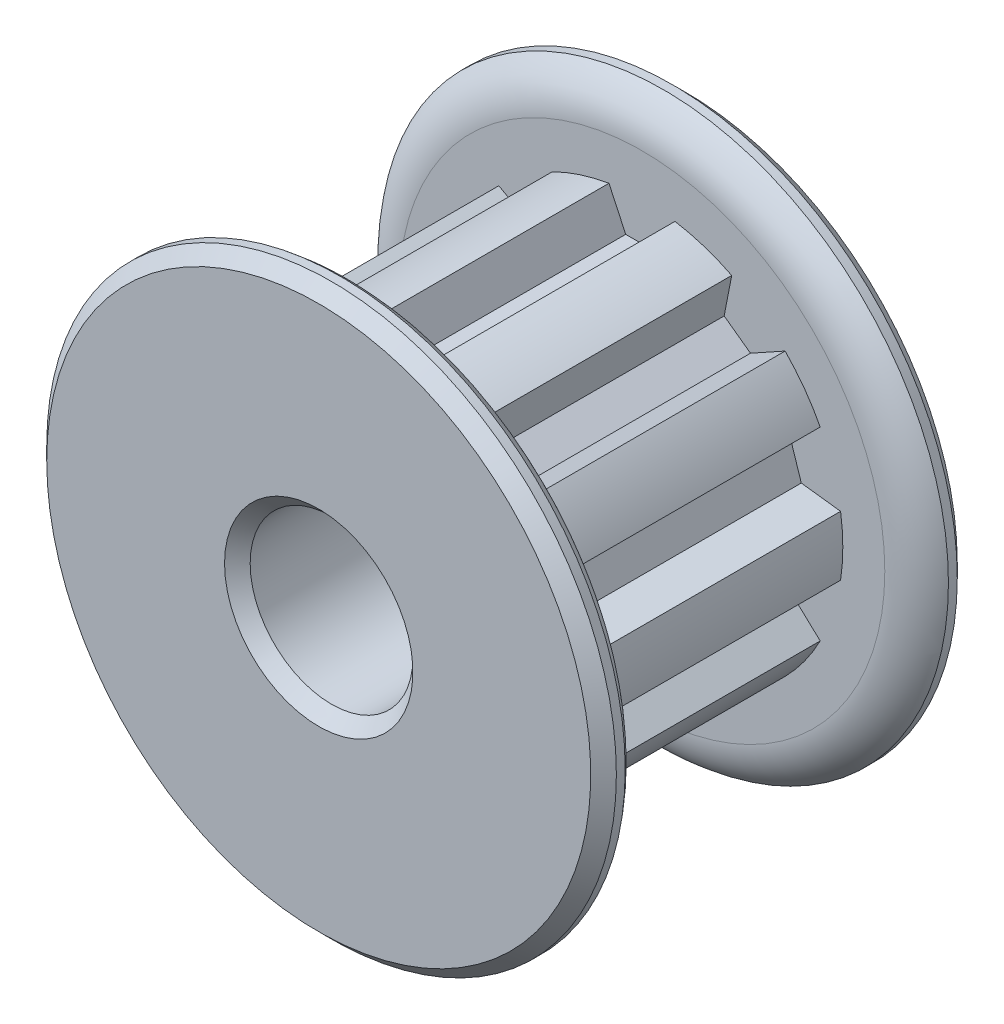
SolidWorks part; units mm, degrees
ref_plane "Front Plane" through (0, 0, 0) normal (0, 0, 1) x (1, 0, 0)
ref_plane "Top Plane" through (0, 0, 0) normal (0, 1, 0) x (1, 0, 0)
ref_plane "Right Plane" through (0, 0, 0) normal (1, 0, 0) x (0, 0, -1)
sketch "Sketch1" plane through (0, 0, 0) normal (0, 0, 1) x (1, 0, 0)
  line L0 (-1.2878, 7.7293) -> (-0.635, 6.3293)
  line L1 (-0.635, 6.3293) -> (0.635, 6.3293)
  line L2 (0.635, 6.3293) -> (1.2878, 7.7293)
  line L3 (-1.2878, 7.7293) -> (1.2878, 7.7293)
  line L4 (0, 0) -> (0, 6.3293) construction
  line L5 (0, 6.3293) -> (0, 8.6153) construction
  circle A0 centre (0, 0) radius 8.0899 construction
  circle A1 centre (0, 0) radius 11.1125 construction
  circle A2 centre (0, 0) radius 7.8359 construction
  point P6 (0, 7.7293)
  point P11 (0, 8.0899)
  point P13 (0, 11.1125)
  point P14 (0, 7.8359)
  dimension "D1" = 1.4
  dimension "PD" = 16.1798
  dimension "OD" = 22.225
  dimension "D3" = 1.27
  dimension "Gear OD" = 15.6718
  dimension "b" = 50
  dimension "hs" = 2.286
sketch "Sketch2" plane through (0, 0, 0) normal (1, 0, 0) x (0, 0, -1)
  line L0 (-3.9878, 3.175) -> (10.3124, 3.175)
  line L4 (-3.9878, 11.1125) -> (-2.2987, 11.1125) construction
  line L5 (-2.2987, 11.1125) -> (-2.2987, 7.8359) construction
  line L6 (-2.2987, 7.8359) -> (8.6233, 7.8359)
  line L7 (8.6233, 7.8359) -> (8.6233, 11.1125) construction
  line L8 (8.6233, 11.1125) -> (10.3124, 11.1125) construction
  line L9 (10.3124, 11.1125) -> (10.3124, 3.175)
  line L10 (-10.3124, 0) -> (10.3124, 0) construction
  line L11 (-3.9878, 3.175) -> (-3.9878, 11.1125)
  line L13 (-3.9878, 11.1125) -> (-3.1432, 11.1125)
  line L14 (-2.2987, 9.4742) -> (-2.2987, 7.8359)
  line L15 (8.6233, 7.8359) -> (8.6233, 9.4742)
  line L16 (9.4679, 11.1125) -> (10.3124, 11.1125)
  arc A0 (-2.2987, 9.4742) -> (-3.1432, 11.1125) centre (-4.31, 9.4742) ccw
  arc A1 (8.6233, 9.4742) -> (9.4679, 11.1125) centre (10.6346, 9.4742) cw
  point P12 (-2.2987, 9.4742)
  point P14 (-3.1432, 11.1125)
  point P20 (8.6233, 9.4742)
  point P21 (9.4679, 11.1125)
  point P25 (8.6233, 0)
  point P26 (-2.2987, 0)
  dimension "D1" = 14.3002
  dimension "OA" = 20.6248
  dimension "Bore" = 6.35
  dimension "Inside Width" = 10.922
revolve "Revolve1" add sketch "Sketch2" angle 360 mid plane about L10
sketch "Sketch3" plane through (0, 0, 0) normal (0, 0, 1) x (1, 0, 0)
  line L0 (-0.635, 6.3293) -> (0.635, 6.3293) construction
  line L1 (0.635, 6.3293) -> (1.2878, 7.7293) construction
  line L2 (-1.2878, 7.7293) -> (-0.635, 6.3293) construction
  line L3 (-0.635, 6.3293) -> (0.635, 6.3293)
  line L4 (0.635, 6.3293) -> (1.2878, 7.7293)
  line L5 (-1.2878, 7.7293) -> (-0.635, 6.3293)
  circle A0 centre (0, 0) radius 7.8359 construction
  arc A1 (1.2878, 7.7293) -> (-1.2878, 7.7293) centre (0, 0) ccw
extrude "Cut-Extrude1" cut sketch "Sketch3" against normal up to vertex (8.6233 mm away) from vertex up to point (0, 7.8359, -8.6233) starting at point (0, 7.8359, 2.2987)
fillet "Fillet1" [suppressed] radius 0.61
pattern_circular "CirPattern1" count 10 over 360 about axis through (0, 0, 10.3124) along (0, 0, 1) of "Cut-Extrude1", "Fillet1"
sketch "Sketch4" plane through (0, 0, 0) normal (0, 1, 0) x (1, 0, 0)
  line L0 (0, -3.9878) -> (0, -10.3124) construction
  circle A0 centre (0, -7.1501) radius 2.0828
  dimension "D1" = 4.1656
ref_plane "Plane1" through (0, 0, 7.1501) normal (0, 0, 1) x (1, 0, 0)
ref_plane "Contact Plane 2" through (0, 0, -10.3124) normal (0, 0, -1) x (-1, 0, 0)
ref_axis "Center Axis 1" through (0, 0, -10.3124) along (0, 0, 1)
chamfer "Chamfer1" distance 0.5 angle 45 4 edges at (3.175, 0, -10.3124) (11.1125, 0, -10.3124) (11.1125, 0, 3.9878) (3.175, 0, 3.9878)
